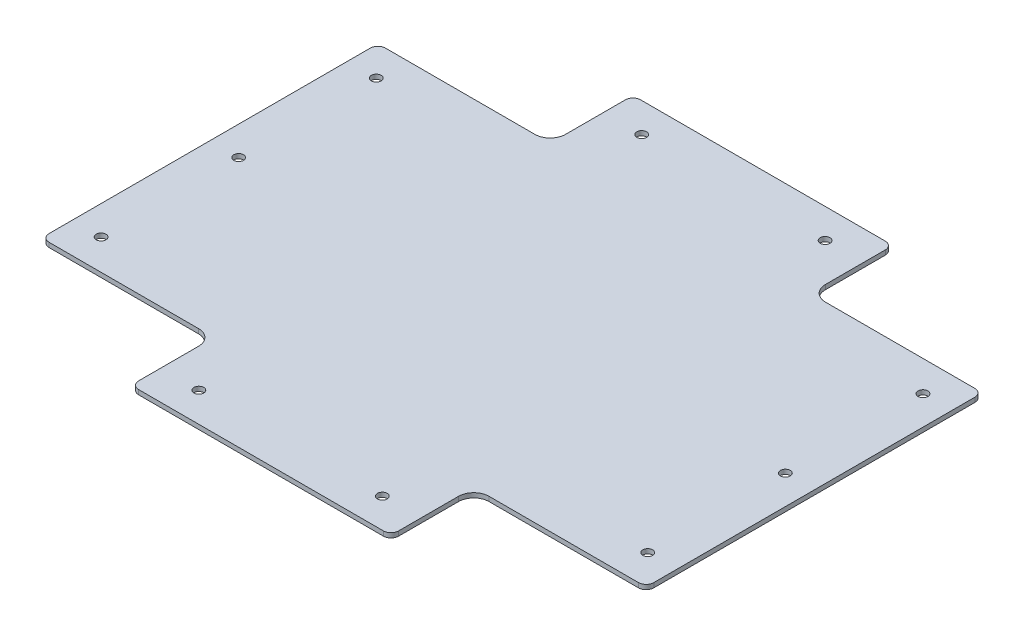
SolidWorks part; units mm, degrees
material "7075-T6, Пластина (SS)"
ref_plane "Спереди" through (0, 0, 0) normal (0, 0, 1) x (1, 0, 0)
ref_plane "Сверху" through (0, 0, 0) normal (0, 1, 0) x (1, 0, 0)
ref_plane "Справа" through (0, 0, 0) normal (1, 0, 0) x (0, 0, -1)
sketch "Эскиз1" plane through (0, 0, 0) normal (0, 1, 0) x (1, 0, 0)
  line L1 (-80, -164.1263) -> (80, -164.1263)
  line L2 (-197.7178, -105) -> (-197.7178, 105)
  line L3 (-80, 164.1263) -> (80, 164.1263)
  line L4 (197.7178, -105) -> (197.7178, 105)
  line L5 (-236.4266, 144.4996) -> (-147.9018, 144.4996) construction
  line L6 (-147.9018, 144.4996) -> (286.4952, 144.4996) construction
  line L18 (-284.5497, 0) -> (284.3305, 0) construction
  line L19 (-160.9018, 110) -> (-134.9018, 110)
  line L20 (-160.9018, 110) -> (-160.9018, 0)
  line L21 (-160.9018, 0) -> (-134.9018, 0)
  line L22 (-134.9018, 110) -> (-134.9018, 0)
  line L23 (-147.9018, -182.6295) -> (-147.9018, 219.9923) construction
  line L24 (-160.9018, 0) -> (-134.9018, 0)
  line L25 (-160.9018, 0) -> (-160.9018, -110)
  line L26 (-160.9018, -110) -> (-134.9018, -110)
  line L27 (-134.9018, 0) -> (-134.9018, -110)
  line L28 (-97.9018, -119.4996) -> (-197.9018, -119.4996)
  line L29 (-97.9018, 169.4996) -> (-197.9018, 169.4996)
  line L30 (-97.9018, 169.4996) -> (-97.9018, 119.4996)
  line L31 (-97.9018, 119.4996) -> (-197.9018, 119.4996)
  line L32 (-197.9018, 169.4996) -> (-197.9018, 119.4996)
  line L33 (-97.9018, 169.4996) -> (-197.9018, 119.4996) construction
  line L34 (-97.9018, 119.4996) -> (-197.9018, 169.4996) construction
  line L35 (-197.9018, -169.4996) -> (-197.9018, -119.4996)
  line L36 (-97.9018, -169.4996) -> (-197.9018, -169.4996)
  line L37 (-97.9018, -169.4996) -> (-97.9018, -119.4996)
  line L39 (-85, 120) -> (-85, 159.1263)
  line L40 (0, 262.7398) -> (0, -186.5795) construction
  line L41 (-192.7178, 110) -> (-95, 110)
  line L43 (-192.7178, -110) -> (-95, -110)
  line L44 (-85, -120) -> (-85, -159.1263)
  line L45 (85, 120) -> (85, 159.1263)
  line L46 (192.7178, 110) -> (95, 110)
  line L47 (192.7178, -110) -> (95, -110)
  line L48 (85, -120) -> (85, -159.1263)
  line L49 (97.9018, -169.4996) -> (97.9018, -119.4996)
  line L50 (97.9018, -169.4996) -> (197.9018, -169.4996)
  line L51 (197.9018, -169.4996) -> (197.9018, -119.4996)
  line L52 (97.9018, -119.4996) -> (197.9018, -119.4996)
  line L53 (160.9018, 0) -> (160.9018, -110)
  line L54 (160.9018, -110) -> (134.9018, -110)
  line L55 (134.9018, 0) -> (134.9018, -110)
  line L56 (160.9018, 0) -> (134.9018, 0)
  line L57 (160.9018, 110) -> (160.9018, 0)
  line L58 (160.9018, 0) -> (134.9018, 0)
  line L59 (134.9018, 110) -> (134.9018, 0)
  line L60 (160.9018, 110) -> (134.9018, 110)
  line L61 (97.9018, 119.4996) -> (197.9018, 119.4996)
  line L62 (197.9018, 169.4996) -> (197.9018, 119.4996)
  line L63 (97.9018, 169.4996) -> (197.9018, 169.4996)
  line L64 (97.9018, 169.4996) -> (97.9018, 119.4996)
  line L65 (60, -144.8055) -> (-60, -144.8055) construction
  line L66 (-178.7687, -90) -> (-178.7687, 90) construction
  arc A0 (85, -120) -> (95, -110) centre (95, -120) cw
  arc A1 (85, 120) -> (95, 110) centre (95, 120) ccw
  arc A2 (-95, -110) -> (-85, -120) centre (-95, -120) cw
  arc A3 (-85, 120) -> (-95, 110) centre (-95, 120) cw
  arc A4 (192.7178, -110) -> (197.7178, -105) centre (192.7178, -105) ccw
  arc A5 (85, -159.1263) -> (80, -164.1263) centre (80, -159.1263) cw
  arc A6 (-85, -159.1263) -> (-80, -164.1263) centre (-80, -159.1263) ccw
  arc A7 (-192.7178, -110) -> (-197.7178, -105) centre (-192.7178, -105) cw
  arc A8 (-192.7178, 110) -> (-197.7178, 105) centre (-192.7178, 105) ccw
  arc A9 (197.7178, 105) -> (192.7178, 110) centre (192.7178, 105) ccw
  arc A10 (85, 159.1263) -> (80, 164.1263) centre (80, 159.1263) ccw
  arc A11 (-85, 159.1263) -> (-80, 164.1263) centre (-80, 159.1263) cw
  circle A12 centre (60, 144.8055) radius 3.2
  circle A13 centre (60, -144.8055) radius 3.2
  circle A14 centre (-60, -144.8055) radius 3.2
  circle A15 centre (-60, 144.8055) radius 3.2
  circle A16 centre (-178.7687, 90) radius 3.2
  circle A17 centre (-178.7687, -90) radius 3.2
  circle A18 centre (-178.7687, 0) radius 3.2
  circle A19 centre (178.7687, 90) radius 3.2
  circle A20 centre (178.7687, 0) radius 3.2
  circle A21 centre (178.7687, -90) radius 3.2
  point P0 (0, 0)
  point P3 (85, -110)
  point P17 (-147.9018, 110)
  point P18 (-147.9018, 110)
  point P20 (-147.9018, 0)
  point P22 (-150, 134)
  point P37 (-147.9018, 144.4996)
  point P46 (85, 110)
  point P52 (-85, -110)
  point P55 (-85, 110)
  point P56 (-147.9018, 0)
  point P58 (0, 0)
  point P59 (-178.7687, 0)
  point P62 (178.7687, 90)
  point P77 (197.7178, -110)
  point P80 (85, -164.1263)
  point P83 (-85, -164.1263)
  point P86 (-197.7178, -110)
  point P89 (-197.7178, 110)
  point P92 (197.7178, 110)
  point P95 (85, 164.1263)
  point P98 (-85, 164.1263)
  point P99 (178.7687, 0)
  point P100 (60, 144.8055)
  point P101 (178.7687, -90)
  point P103 (-60, 144.8055)
  point P110 (-23.4948, -139.1615)
  point P111 (0, 0)
  point P112 (0, 0)
  point P115 (0, 0)
  point P116 (0, 0)
  point P119 (0, 0)
  point P120 (0, 0)
  point P122 (0, 0)
  point P124 (0, 0)
  point P125 (0, 0)
  point P126 (0, 0)
  point P127 (0, 0)
  point P128 (0, 0)
  dimension "D2" = 50
  dimension "D6" = 10
  dimension "D11" = 60
  dimension "D12" = 60
  dimension "D4" = 5
  dimension "D3" = 26
  dimension "D5" = 338.9991
  dimension "D7" = 395.4357
  dimension "D8" = 110
  dimension "D9" = 170
  dimension "D10" = 100
  dimension "D13" = 9.4996
  dimension "D14" = 12.9018
  dimension "D15" = 90
  dimension "D16" = 90
sketch "Эскиз2" plane through (0, 0, 0) normal (0, 1, 0) x (1, 0, 0)
  line L0 (-162.9105, 114) -> (-136.9105, 114)
  line L1 (-162.9105, 114) -> (-162.9105, 0)
  line L2 (-162.9105, 0) -> (-136.9105, 0)
  line L3 (-136.9105, 114) -> (-136.9105, 0)
  line L4 (-149.9105, -192.6295) -> (-149.9105, 209.9923) construction
  line L5 (-162.9105, 0) -> (-136.9105, 0)
  line L6 (-162.9105, 0) -> (-162.9105, -114)
  line L7 (-162.9105, -114) -> (-136.9105, -114)
  line L8 (-136.9105, 0) -> (-136.9105, -114)
  line L9 (-99.9105, -123.5568) -> (-199.9105, -123.5568)
  line L10 (-99.9105, 163.4996) -> (-199.9105, 163.4996)
  line L11 (-99.9105, 163.4996) -> (-99.9105, 123.4996)
  line L12 (-99.9105, 123.4996) -> (-199.9105, 123.4996)
  line L13 (-199.9105, 163.4996) -> (-199.9105, 123.4996)
  line L14 (-199.9105, -163.5568) -> (-199.9105, -123.5568)
  line L15 (-99.9105, -163.5568) -> (-199.9105, -163.5568)
  line L16 (-99.9105, -163.5568) -> (-99.9105, -123.5568)
  line L17 (-284.5497, 0) -> (284.3305, 0) construction
  point P11 (-149.9105, 0)
  point P12 (-149.9105, 0)
sketch "Эскиз3" plane through (0, 0, 0) normal (0, 1, 0) x (1, 0, 0)
  line L0 (-89.8176, -177.9027) -> (70.2405, -177.9027)
  line L1 (-209.7886, -106.9112) -> (-209.7886, 106.8353)
  line L2 (-80.029, 172.0973) -> (50.2405, 172.0973)
  line L3 (170.2114, -106.9112) -> (170.2114, 103.9123)
  line L4 (-87.1938, 124.0033) -> (-87.1938, 164.9326)
  line L5 (-202.6239, 114) -> (-97.1971, 114)
  line L6 (-202.6239, -114.076) -> (-106.9857, -114.076)
  line L7 (-96.9823, -124.0793) -> (-96.9823, -170.738)
  line L8 (57.4052, 121.0803) -> (57.4052, 164.9326)
  line L9 (163.0467, 111.077) -> (67.4085, 111.077)
  line L10 (163.0467, -114.076) -> (87.4085, -114.076)
  line L11 (77.4052, -124.0793) -> (77.4052, -170.738)
  line L13 (-162.9105, 114) -> (-136.9105, 114) construction
  arc A0 (77.4052, -124.0793) -> (87.4085, -114.076) centre (87.4085, -124.0793) cw
  arc A1 (57.4052, 121.0803) -> (67.4085, 111.077) centre (67.4085, 121.0803) ccw
  arc A2 (-106.9857, -114.076) -> (-96.9823, -124.0793) centre (-106.9857, -124.0793) cw
  arc A3 (-87.1938, 124.0033) -> (-97.1971, 114) centre (-97.1971, 124.0033) cw
  arc A4 (-80.029, 172.0973) -> (-87.1938, 164.9326) centre (-80.029, 164.9326) ccw
  arc A5 (50.2405, 172.0973) -> (57.4052, 164.9326) centre (50.2405, 164.9326) cw
  arc A6 (170.2114, 103.9123) -> (163.0467, 111.077) centre (163.0467, 103.9123) ccw
  arc A7 (170.2114, -106.9112) -> (163.0467, -114.076) centre (163.0467, -106.9112) cw
  arc A8 (70.2405, -177.9027) -> (77.4052, -170.738) centre (70.2405, -170.738) ccw
  arc A9 (-89.8176, -177.9027) -> (-96.9823, -170.738) centre (-89.8176, -170.738) cw
  arc A10 (-209.7886, -106.9112) -> (-202.6239, -114.076) centre (-202.6239, -106.9112) ccw
  arc A11 (-209.7886, 106.8353) -> (-202.6239, 114) centre (-202.6239, 106.8353) cw
  point P36 (115.2276, 111.077)
  point P39 (-149.9105, 114)
  point P42 (-149.9105, 114)
  dimension "D3" = 10.0033
  dimension "D4" = 7.1647
  dimension "D1" = 380
  dimension "D2" = 350
  dimension "D5" = 112.8062
  dimension "D6" = 63.8267
  dimension "D7" = 61.0203
extrude "Бобышка-Вытянуть1" add sketch "Эскиз1" along normal blind 3 separate body contours A11 L39 A3 L41 L22 L27 L43 A2 L44 A6 L1 A5 L48 A0 L47 L55 L59 L46 A1 L45 A10 L3 | L4 A9 L46 L57 L53 L47 A4 | L46 L59 L56 L57 | L53 L56 L55 L47 | L27 L21 L25 L26 | L41 A8 L2 A7 L43 L25 L20 | L22 L19 L20 L21 region at (0, 0, 0) region at (-147.9018, 0, 55) region at (147.9018, 0, 55) region at (-176.8098, 0, 107.7694) region at (-147.9018, 0, -55) region at (163.1324, 0, 55) region at (147.9018, 0, -55)
